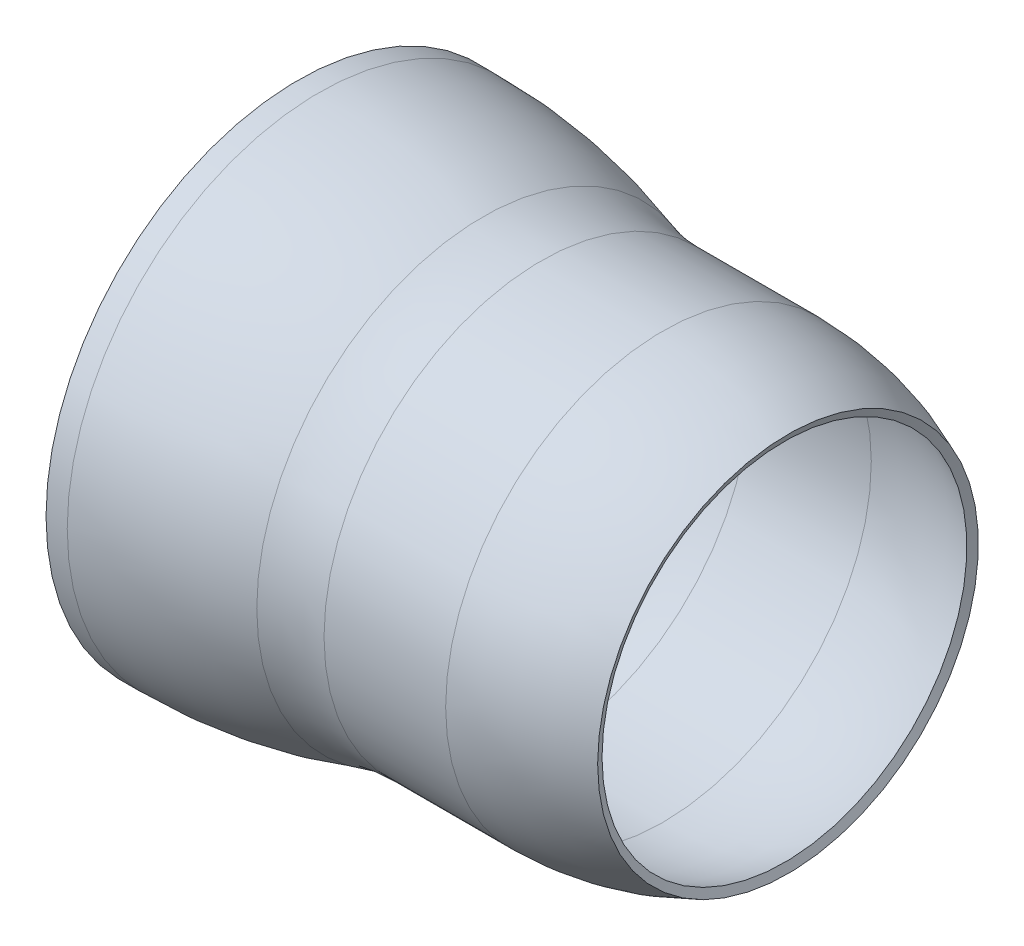
SolidWorks part; units mm, degrees
ref_plane "Front Plane" through (0, 0, 0) normal (0, 0, 1) x (1, 0, 0)
ref_plane "Top Plane" through (0, 0, 0) normal (0, 1, 0) x (1, 0, 0)
ref_plane "Right Plane" through (0, 0, 0) normal (1, 0, 0) x (0, 0, -1)
sketch "Sketch1" plane through (0, 0, 0) normal (0, 0, 1) x (1, 0, 0)
  line L0 (0, 0) -> (0, 140)
  line L1 (0, 140) -> (12.209, 140)
  line L2 (0, 0) -> (280, 0) construction
  line L3 (280, 0) -> (280, 105)
  line L5 (140, 120) -> (210, 120)
  line L6 (0, 145) -> (12.209, 145)
  line L7 (140, 125) -> (210, 125)
  line L8 (0, 145) -> (0, 140)
  line L9 (280, 105) -> (282.0488, 109.561)
  arc A0 (12.209, 140) -> (105, 125.4777) centre (12.209, -163.7076) cw
  arc A2 (140, 120) -> (105, 125.4777) centre (140, 234.556) cw
  arc A3 (210, 120) -> (280, 105) centre (210, -50.8333) cw
  arc A4 (12.209, 145) -> (106.5276, 130.2386) centre (12.209, -163.7076) cw
  arc A5 (140, 125) -> (106.5276, 130.2386) centre (140, 234.556) cw
  arc A6 (210, 125) -> (282.0488, 109.561) centre (210, -50.8333) cw
  dimension "D1" = 140
  dimension "D2" = 105
  dimension "D3" = 280
  dimension "D5" = 12.209
  dimension "D6" = 175
  dimension "D7" = 140
  dimension "D4" = 120
  dimension "D8" = 70
  dimension "D9" = 5
revolve "Revolve1" add sketch "Sketch1" angle 360 about L2 region at (2.8487, 142.5, 0)
equation "\"ThrusterDim\"= 140mm"
equation "\"D1@Sketch1\"=\"ThrusterDim\""
equation "\"D2@Sketch1\"=.75 * \"ThrusterDim\""
equation "\"D3@Sketch1\"=2 * \"ThrusterDim\""
equation "\"D6@Sketch1\"=\"ThrusterDim\" * 1.25"
equation "\"D7@Sketch1\"=\"ThrusterDim\""
equation "\"D4@Sketch1\"=\"ThrusterDim\"* 0.85714286"
equation "\"hatchHoleDiameter\"= 600mm"
equation "\"hullThickness\"= 120mm"
equation "\"gasketHullInterconnectWidth\"= 100mm"
equation "\"collarThickness\"= 15"
equation "\"hatchTunnelLength\"=200"
equation "\"oRingDiameter\"=2"
equation "\"boltPatternRadiusInterconnect\"=500"
equation "\"interconnectBoltDiameter\"=30"
equation "\"hatchShaftDiameter\"=20"
equation "\"hatchMinima\"=50"
equation "\"hullDiameter\"=2000"
equation "\"hatchMaxima\"=180"
equation "\"bushingFlatHatch\"=15"
equation "\"hingePivotDiameter\"=20"
equation "\"handleWidth\"=250"
equation "\"handleHeight\"=160"
equation "\"handleThickness\"=25"
equation "\"FrameLength\"= 4300"
equation "\"FrameMidLength\"= 3000"
equation "\"TubeOD\"= 100"
equation "\"FrameBackFlat\"= 800"
equation "\"TubeWall\"=15"
equation "\"TopMemberAngle\"=120"
equation "\"FrameHight\"= 2500"
